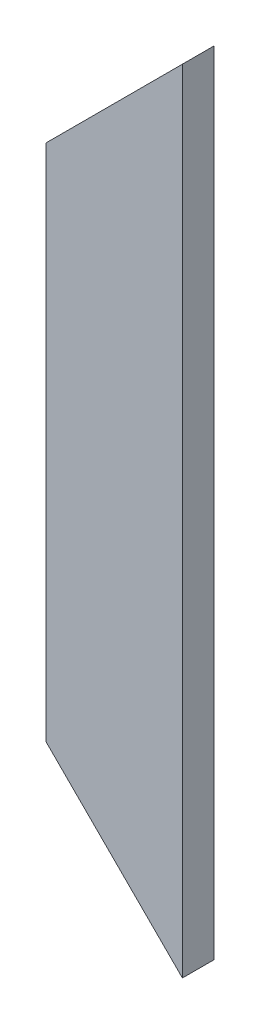
SolidWorks part; units mm, degrees
ref_plane "Front Plane" through (0, 0, 0) normal (0, 0, 1) x (1, 0, 0)
ref_plane "Top Plane" through (0, 0, 0) normal (0, 1, 0) x (1, 0, 0)
ref_plane "Right Plane" through (0, 0, 0) normal (1, 0, 0) x (0, 0, -1)
sketch "Sketch1" plane through (0, 0, 0) normal (0, 0, 1) x (1, 0, 0)
  line L0 (-13, -24.75) -> (-13, 24.75)
  line L5 (55, 0) -> (-55, 0) construction
  line L6 (-13, 24.75) -> (0, 37.75)
  line L7 (0, -55) -> (0, 55) construction
  line L8 (0, 37.75) -> (0, -37.75)
  line L9 (-13, -24.75) -> (0, -37.75)
  point P10 (0, 0)
  point P11 (-13, 0)
  dimension "D3" = 45
  dimension "D1" = 13
  dimension "D2" = 49.5
extrude "Boss-Extrude1" add sketch "Sketch1" along normal blind 3 contours L0 L9 L8 L6 region at (-6.0493, 0, 0)
